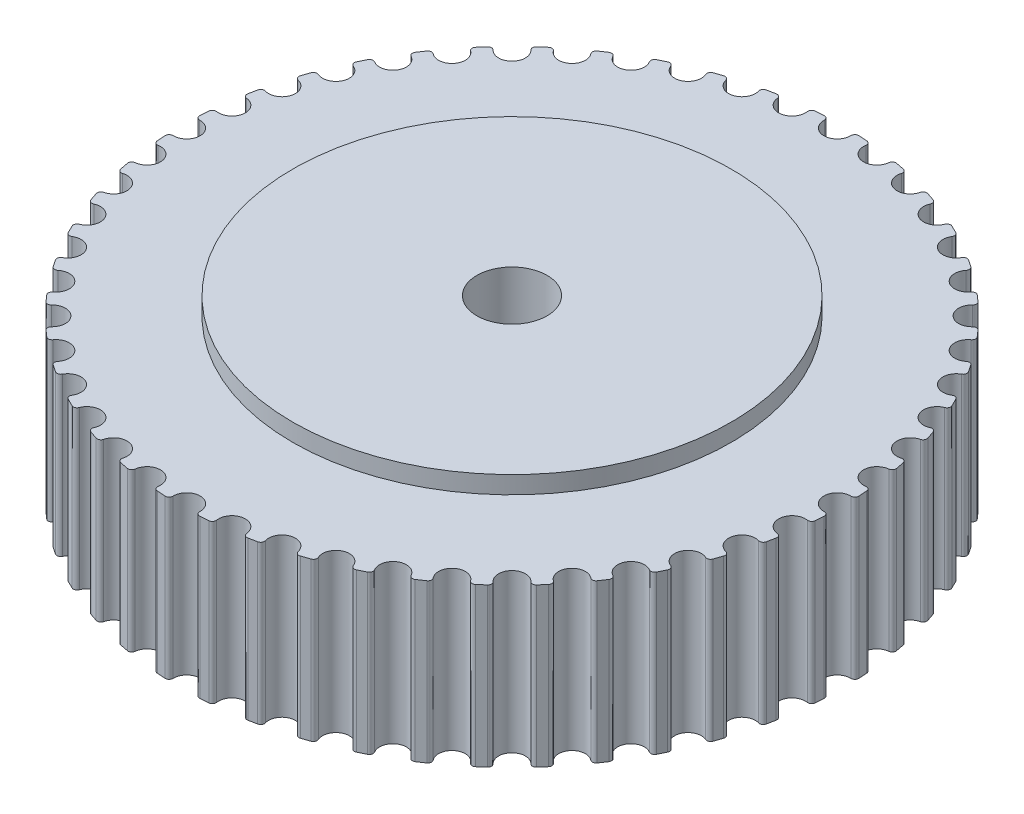
SolidWorks part; units mm, degrees
ref_plane "Ebene vorne" through (0, 0, 0) normal (0, 0, 1) x (1, 0, 0)
ref_plane "Ebene oben" through (0, 0, 0) normal (0, 1, 0) x (1, 0, 0)
ref_plane "Ebene rechts" through (0, 0, 0) normal (1, 0, 0) x (0, 0, -1)
sketch "Skizze1" plane through (0, 0, 0) normal (0, 1, 0) x (1, 0, 0)
  line L0 (0, 0) -> (27482.8107, 0) construction
  line L1 (0, 0) -> (0, 27482.8107) construction
  line L2 (0, 0) -> (8.3206, 63.2012) construction
  line L3 (1.9824, 37.5727) -> (2.9388, 37.51)
  line L4 (6.8697, 36.9925) -> (7.8097, 36.8055)
  line L5 (11.6394, 35.7794) -> (12.547, 35.4713)
  line L6 (16.2099, 33.954) -> (17.0696, 33.5301)
  line L7 (20.5032, 31.5477) -> (21.3001, 31.0152)
  line L8 (24.4455, 28.6016) -> (25.1662, 27.9697)
  line L9 (27.9697, 25.1662) -> (28.6016, 24.4455)
  line L10 (31.0152, 21.3001) -> (31.5477, 20.5032)
  line L11 (33.5301, 17.0696) -> (33.954, 16.2099)
  line L12 (35.4713, 12.547) -> (35.7794, 11.6394)
  line L13 (36.8055, 7.8097) -> (36.9925, 6.8697)
  line L14 (37.51, 2.9388) -> (37.5727, 1.9824)
  line L15 (37.5727, -1.9824) -> (37.51, -2.9388)
  line L16 (36.9925, -6.8697) -> (36.8055, -7.8097)
  line L17 (35.7794, -11.6394) -> (35.4713, -12.547)
  line L18 (33.954, -16.2099) -> (33.5301, -17.0696)
  line L19 (31.5477, -20.5032) -> (31.0152, -21.3001)
  line L20 (28.6016, -24.4455) -> (27.9697, -25.1662)
  line L21 (25.1662, -27.9697) -> (24.4455, -28.6016)
  line L22 (21.3001, -31.0152) -> (20.5032, -31.5477)
  line L23 (17.0696, -33.5301) -> (16.2099, -33.954)
  line L24 (12.547, -35.4713) -> (11.6394, -35.7794)
  line L25 (7.8097, -36.8055) -> (6.8697, -36.9925)
  line L26 (2.9388, -37.51) -> (1.9824, -37.5727)
  line L27 (-1.9824, -37.5727) -> (-2.9388, -37.51)
  line L28 (-6.8697, -36.9925) -> (-7.8097, -36.8055)
  line L29 (-11.6394, -35.7794) -> (-12.547, -35.4713)
  line L30 (-16.2099, -33.954) -> (-17.0696, -33.5301)
  line L31 (-20.5032, -31.5477) -> (-21.3001, -31.0152)
  line L32 (-24.4455, -28.6016) -> (-25.1662, -27.9697)
  line L33 (-27.9697, -25.1662) -> (-28.6016, -24.4455)
  line L34 (-31.0152, -21.3001) -> (-31.5477, -20.5032)
  line L35 (-33.5301, -17.0696) -> (-33.954, -16.2099)
  line L36 (-35.4713, -12.547) -> (-35.7794, -11.6394)
  line L37 (-36.8055, -7.8097) -> (-36.9925, -6.8697)
  line L38 (-37.51, -2.9388) -> (-37.5727, -1.9824)
  line L39 (-37.5727, 1.9824) -> (-37.51, 2.9388)
  line L40 (-36.9925, 6.8697) -> (-36.8055, 7.8097)
  line L41 (-35.7794, 11.6394) -> (-35.4713, 12.547)
  line L42 (-33.954, 16.2099) -> (-33.5301, 17.0696)
  line L43 (-31.5477, 20.5032) -> (-31.0152, 21.3001)
  line L44 (-28.6016, 24.4455) -> (-27.9697, 25.1662)
  line L45 (-25.1662, 27.9697) -> (-24.4455, 28.6016)
  line L46 (-21.3001, 31.0152) -> (-20.5032, 31.5477)
  line L47 (-17.0696, 33.5301) -> (-16.2099, 33.954)
  line L48 (-12.547, 35.4713) -> (-11.6394, 35.7794)
  line L49 (-7.8097, 36.8055) -> (-6.8697, 36.9925)
  line L50 (-2.9388, 37.51) -> (-1.9824, 37.5727)
  circle A0 centre (0, 0) radius 37.625 construction
  circle A1 centre (0, 0) radius 35.565 construction
  arc A2 (0, 35.565) -> (1.5244, 37.1318) centre (0, 37.09) ccw
  arc A3 (1.9824, 37.5727) -> (1.5244, 37.1318) centre (1.9543, 37.1436) ccw
  arc A4 (3.3353, 37.0131) -> (4.6422, 35.2607) centre (4.8412, 36.7727) ccw
  arc A5 (3.3353, 37.0131) -> (2.9388, 37.51) centre (2.9107, 37.0809) ccw
  arc A6 (8.1379, 36.2611) -> (9.2049, 34.3532) centre (9.5996, 35.8262) ccw
  arc A7 (8.1379, 36.2611) -> (7.8097, 36.8055) centre (7.7258, 36.3838) ccw
  arc A8 (6.8697, 36.9925) -> (6.3581, 36.6152) centre (6.7858, 36.5708) ccw
  arc A9 (4.6422, 35.2607) -> (6.3581, 36.6152) centre (4.8412, 36.7727) ccw
  arc A10 (12.8014, 34.8887) -> (13.6101, 32.8578) centre (14.1937, 34.2667) ccw
  arc A11 (12.8014, 34.8887) -> (12.547, 35.4713) centre (12.4087, 35.0641) ccw
  arc A12 (11.6394, 35.7794) -> (11.0829, 35.472) centre (11.5012, 35.3722) ccw
  arc A13 (9.2049, 34.3532) -> (11.0829, 35.472) centre (9.5996, 35.8262) ccw
  arc A14 (17.2457, 32.9193) -> (17.7825, 30.8002) centre (18.545, 32.1209) ccw
  arc A15 (17.2457, 32.9193) -> (17.0696, 33.5301) centre (16.8794, 33.1445) ccw
  arc A16 (16.2099, 33.954) -> (15.6181, 33.722) centre (16.0198, 33.5684) ccw
  arc A17 (13.6101, 32.8578) -> (15.6181, 33.722) centre (14.1937, 34.2667) ccw
  arc A18 (21.395, 30.3867) -> (21.6506, 28.2156) centre (22.579, 29.4255) ccw
  arc A19 (21.395, 30.3867) -> (21.3001, 31.0152) centre (21.0612, 30.6577) ccw
  arc A20 (20.5032, 31.5477) -> (19.8861, 31.3949) centre (20.2643, 31.1902) ccw
  arc A21 (17.7825, 30.8002) -> (19.8861, 31.3949) centre (18.545, 32.1209) ccw
  arc A22 (25.1782, 27.3341) -> (25.1483, 25.1483) centre (26.2266, 26.2266) ccw
  arc A23 (25.1782, 27.3341) -> (25.1662, 27.9697) centre (24.8826, 27.6464) ccw
  arc A24 (24.4455, 28.6016) -> (23.8138, 28.5306) centre (24.162, 28.2783) ccw
  arc A25 (21.6506, 28.2156) -> (23.8138, 28.5306) centre (22.579, 29.4255) ccw
  arc A26 (28.5306, 23.8138) -> (28.2156, 21.6506) centre (29.4255, 22.579) ccw
  arc A27 (28.5306, 23.8138) -> (28.6016, 24.4455) centre (28.2783, 24.162) ccw
  arc A28 (27.9697, 25.1662) -> (27.3341, 25.1782) centre (27.6464, 24.8826) ccw
  arc A29 (25.1483, 25.1483) -> (27.3341, 25.1782) centre (26.2266, 26.2266) ccw
  arc A30 (31.3949, 19.8861) -> (30.8002, 17.7825) centre (32.1209, 18.545) ccw
  arc A31 (31.3949, 19.8861) -> (31.5477, 20.5032) centre (31.1902, 20.2643) ccw
  arc A32 (31.0152, 21.3001) -> (30.3867, 21.395) centre (30.6577, 21.0612) ccw
  arc A33 (28.2156, 21.6506) -> (30.3867, 21.395) centre (29.4255, 22.579) ccw
  arc A34 (33.722, 15.6181) -> (32.8578, 13.6101) centre (34.2667, 14.1937) ccw
  arc A35 (33.722, 15.6181) -> (33.954, 16.2099) centre (33.5684, 16.0198) ccw
  arc A36 (33.5301, 17.0696) -> (32.9193, 17.2457) centre (33.1445, 16.8794) ccw
  arc A37 (30.8002, 17.7825) -> (32.9193, 17.2457) centre (32.1209, 18.545) ccw
  arc A38 (35.472, 11.0829) -> (34.3532, 9.2049) centre (35.8262, 9.5996) ccw
  arc A39 (35.472, 11.0829) -> (35.7794, 11.6394) centre (35.3722, 11.5012) ccw
  arc A40 (35.4713, 12.547) -> (34.8887, 12.8014) centre (35.0641, 12.4087) ccw
  arc A41 (32.8578, 13.6101) -> (34.8887, 12.8014) centre (34.2667, 14.1937) ccw
  arc A42 (36.6152, 6.3581) -> (35.2607, 4.6422) centre (36.7727, 4.8412) ccw
  arc A43 (36.6152, 6.3581) -> (36.9925, 6.8697) centre (36.5708, 6.7858) ccw
  arc A44 (36.8055, 7.8097) -> (36.2611, 8.1379) centre (36.3838, 7.7258) ccw
  arc A45 (34.3532, 9.2049) -> (36.2611, 8.1379) centre (35.8262, 9.5996) ccw
  arc A46 (37.1318, 1.5244) -> (35.565, 0) centre (37.09, 0) ccw
  arc A47 (37.1318, 1.5244) -> (37.5727, 1.9824) centre (37.1436, 1.9543) ccw
  arc A48 (37.51, 2.9388) -> (37.0131, 3.3353) centre (37.0809, 2.9107) ccw
  arc A49 (35.2607, 4.6422) -> (37.0131, 3.3353) centre (36.7727, 4.8412) ccw
  arc A50 (37.0131, -3.3353) -> (35.2607, -4.6422) centre (36.7727, -4.8412) ccw
  arc A51 (37.0131, -3.3353) -> (37.51, -2.9388) centre (37.0809, -2.9107) ccw
  arc A52 (37.5727, -1.9824) -> (37.1318, -1.5244) centre (37.1436, -1.9543) ccw
  arc A53 (35.565, 0) -> (37.1318, -1.5244) centre (37.09, 0) ccw
  arc A54 (36.2611, -8.1379) -> (34.3532, -9.2049) centre (35.8262, -9.5996) ccw
  arc A55 (36.2611, -8.1379) -> (36.8055, -7.8097) centre (36.3838, -7.7258) ccw
  arc A56 (36.9925, -6.8697) -> (36.6152, -6.3581) centre (36.5708, -6.7858) ccw
  arc A57 (35.2607, -4.6422) -> (36.6152, -6.3581) centre (36.7727, -4.8412) ccw
  arc A58 (34.8887, -12.8014) -> (32.8578, -13.6101) centre (34.2667, -14.1937) ccw
  arc A59 (34.8887, -12.8014) -> (35.4713, -12.547) centre (35.0641, -12.4087) ccw
  arc A60 (35.7794, -11.6394) -> (35.472, -11.0829) centre (35.3722, -11.5012) ccw
  arc A61 (34.3532, -9.2049) -> (35.472, -11.0829) centre (35.8262, -9.5996) ccw
  arc A62 (32.9193, -17.2457) -> (30.8002, -17.7825) centre (32.1209, -18.545) ccw
  arc A63 (32.9193, -17.2457) -> (33.5301, -17.0696) centre (33.1445, -16.8794) ccw
  arc A64 (33.954, -16.2099) -> (33.722, -15.6181) centre (33.5684, -16.0198) ccw
  arc A65 (32.8578, -13.6101) -> (33.722, -15.6181) centre (34.2667, -14.1937) ccw
  arc A66 (30.3867, -21.395) -> (28.2156, -21.6506) centre (29.4255, -22.579) ccw
  arc A67 (30.3867, -21.395) -> (31.0152, -21.3001) centre (30.6577, -21.0612) ccw
  arc A68 (31.5477, -20.5032) -> (31.3949, -19.8861) centre (31.1902, -20.2643) ccw
  arc A69 (30.8002, -17.7825) -> (31.3949, -19.8861) centre (32.1209, -18.545) ccw
  arc A70 (27.3341, -25.1782) -> (25.1483, -25.1483) centre (26.2266, -26.2266) ccw
  arc A71 (27.3341, -25.1782) -> (27.9697, -25.1662) centre (27.6464, -24.8826) ccw
  arc A72 (28.6016, -24.4455) -> (28.5306, -23.8138) centre (28.2783, -24.162) ccw
  arc A73 (28.2156, -21.6506) -> (28.5306, -23.8138) centre (29.4255, -22.579) ccw
  arc A74 (23.8138, -28.5306) -> (21.6506, -28.2156) centre (22.579, -29.4255) ccw
  arc A75 (23.8138, -28.5306) -> (24.4455, -28.6016) centre (24.162, -28.2783) ccw
  arc A76 (25.1662, -27.9697) -> (25.1782, -27.3341) centre (24.8826, -27.6464) ccw
  arc A77 (25.1483, -25.1483) -> (25.1782, -27.3341) centre (26.2266, -26.2266) ccw
  arc A78 (19.8861, -31.3949) -> (17.7825, -30.8002) centre (18.545, -32.1209) ccw
  arc A79 (19.8861, -31.3949) -> (20.5032, -31.5477) centre (20.2643, -31.1902) ccw
  arc A80 (21.3001, -31.0152) -> (21.395, -30.3867) centre (21.0612, -30.6577) ccw
  arc A81 (21.6506, -28.2156) -> (21.395, -30.3867) centre (22.579, -29.4255) ccw
  arc A82 (15.6181, -33.722) -> (13.6101, -32.8578) centre (14.1937, -34.2667) ccw
  arc A83 (15.6181, -33.722) -> (16.2099, -33.954) centre (16.0198, -33.5684) ccw
  arc A84 (17.0696, -33.5301) -> (17.2457, -32.9193) centre (16.8794, -33.1445) ccw
  arc A85 (17.7825, -30.8002) -> (17.2457, -32.9193) centre (18.545, -32.1209) ccw
  arc A86 (11.0829, -35.472) -> (9.2049, -34.3532) centre (9.5996, -35.8262) ccw
  arc A87 (11.0829, -35.472) -> (11.6394, -35.7794) centre (11.5012, -35.3722) ccw
  arc A88 (12.547, -35.4713) -> (12.8014, -34.8887) centre (12.4087, -35.0641) ccw
  arc A89 (13.6101, -32.8578) -> (12.8014, -34.8887) centre (14.1937, -34.2667) ccw
  arc A90 (6.3581, -36.6152) -> (4.6422, -35.2607) centre (4.8412, -36.7727) ccw
  arc A91 (6.3581, -36.6152) -> (6.8697, -36.9925) centre (6.7858, -36.5708) ccw
  arc A92 (7.8097, -36.8055) -> (8.1379, -36.2611) centre (7.7258, -36.3838) ccw
  arc A93 (9.2049, -34.3532) -> (8.1379, -36.2611) centre (9.5996, -35.8262) ccw
  arc A94 (1.5244, -37.1318) -> (0, -35.565) centre (0, -37.09) ccw
  arc A95 (1.5244, -37.1318) -> (1.9824, -37.5727) centre (1.9543, -37.1436) ccw
  arc A96 (2.9388, -37.51) -> (3.3353, -37.0131) centre (2.9107, -37.0809) ccw
  arc A97 (4.6422, -35.2607) -> (3.3353, -37.0131) centre (4.8412, -36.7727) ccw
  arc A98 (-3.3353, -37.0131) -> (-4.6422, -35.2607) centre (-4.8412, -36.7727) ccw
  arc A99 (-3.3353, -37.0131) -> (-2.9388, -37.51) centre (-2.9107, -37.0809) ccw
  arc A100 (-1.9824, -37.5727) -> (-1.5244, -37.1318) centre (-1.9543, -37.1436) ccw
  arc A101 (0, -35.565) -> (-1.5244, -37.1318) centre (0, -37.09) ccw
  arc A102 (-8.1379, -36.2611) -> (-9.2049, -34.3532) centre (-9.5996, -35.8262) ccw
  arc A103 (-8.1379, -36.2611) -> (-7.8097, -36.8055) centre (-7.7258, -36.3838) ccw
  arc A104 (-6.8697, -36.9925) -> (-6.3581, -36.6152) centre (-6.7858, -36.5708) ccw
  arc A105 (-4.6422, -35.2607) -> (-6.3581, -36.6152) centre (-4.8412, -36.7727) ccw
  arc A106 (-12.8014, -34.8887) -> (-13.6101, -32.8578) centre (-14.1937, -34.2667) ccw
  arc A107 (-12.8014, -34.8887) -> (-12.547, -35.4713) centre (-12.4087, -35.0641) ccw
  arc A108 (-11.6394, -35.7794) -> (-11.0829, -35.472) centre (-11.5012, -35.3722) ccw
  arc A109 (-9.2049, -34.3532) -> (-11.0829, -35.472) centre (-9.5996, -35.8262) ccw
  arc A110 (-17.2457, -32.9193) -> (-17.7825, -30.8002) centre (-18.545, -32.1209) ccw
  arc A111 (-17.2457, -32.9193) -> (-17.0696, -33.5301) centre (-16.8794, -33.1445) ccw
  arc A112 (-16.2099, -33.954) -> (-15.6181, -33.722) centre (-16.0198, -33.5684) ccw
  arc A113 (-13.6101, -32.8578) -> (-15.6181, -33.722) centre (-14.1937, -34.2667) ccw
  arc A114 (-21.395, -30.3867) -> (-21.6506, -28.2156) centre (-22.579, -29.4255) ccw
  arc A115 (-21.395, -30.3867) -> (-21.3001, -31.0152) centre (-21.0612, -30.6577) ccw
  arc A116 (-20.5032, -31.5477) -> (-19.8861, -31.3949) centre (-20.2643, -31.1902) ccw
  arc A117 (-17.7825, -30.8002) -> (-19.8861, -31.3949) centre (-18.545, -32.1209) ccw
  arc A118 (-25.1782, -27.3341) -> (-25.1483, -25.1483) centre (-26.2266, -26.2266) ccw
  arc A119 (-25.1782, -27.3341) -> (-25.1662, -27.9697) centre (-24.8826, -27.6464) ccw
  arc A120 (-24.4455, -28.6016) -> (-23.8138, -28.5306) centre (-24.162, -28.2783) ccw
  arc A121 (-21.6506, -28.2156) -> (-23.8138, -28.5306) centre (-22.579, -29.4255) ccw
  arc A122 (-28.5306, -23.8138) -> (-28.2156, -21.6506) centre (-29.4255, -22.579) ccw
  arc A123 (-28.5306, -23.8138) -> (-28.6016, -24.4455) centre (-28.2783, -24.162) ccw
  arc A124 (-27.9697, -25.1662) -> (-27.3341, -25.1782) centre (-27.6464, -24.8826) ccw
  arc A125 (-25.1483, -25.1483) -> (-27.3341, -25.1782) centre (-26.2266, -26.2266) ccw
  arc A126 (-31.3949, -19.8861) -> (-30.8002, -17.7825) centre (-32.1209, -18.545) ccw
  arc A127 (-31.3949, -19.8861) -> (-31.5477, -20.5032) centre (-31.1902, -20.2643) ccw
  arc A128 (-31.0152, -21.3001) -> (-30.3867, -21.395) centre (-30.6577, -21.0612) ccw
  arc A129 (-28.2156, -21.6506) -> (-30.3867, -21.395) centre (-29.4255, -22.579) ccw
  arc A130 (-33.722, -15.6181) -> (-32.8578, -13.6101) centre (-34.2667, -14.1937) ccw
  arc A131 (-33.722, -15.6181) -> (-33.954, -16.2099) centre (-33.5684, -16.0198) ccw
  arc A132 (-33.5301, -17.0696) -> (-32.9193, -17.2457) centre (-33.1445, -16.8794) ccw
  arc A133 (-30.8002, -17.7825) -> (-32.9193, -17.2457) centre (-32.1209, -18.545) ccw
  arc A134 (-35.472, -11.0829) -> (-34.3532, -9.2049) centre (-35.8262, -9.5996) ccw
  arc A135 (-35.472, -11.0829) -> (-35.7794, -11.6394) centre (-35.3722, -11.5012) ccw
  arc A136 (-35.4713, -12.547) -> (-34.8887, -12.8014) centre (-35.0641, -12.4087) ccw
  arc A137 (-32.8578, -13.6101) -> (-34.8887, -12.8014) centre (-34.2667, -14.1937) ccw
  arc A138 (-36.6152, -6.3581) -> (-35.2607, -4.6422) centre (-36.7727, -4.8412) ccw
  arc A139 (-36.6152, -6.3581) -> (-36.9925, -6.8697) centre (-36.5708, -6.7858) ccw
  arc A140 (-36.8055, -7.8097) -> (-36.2611, -8.1379) centre (-36.3838, -7.7258) ccw
  arc A141 (-34.3532, -9.2049) -> (-36.2611, -8.1379) centre (-35.8262, -9.5996) ccw
  arc A142 (-37.1318, -1.5244) -> (-35.565, 0) centre (-37.09, 0) ccw
  arc A143 (-37.1318, -1.5244) -> (-37.5727, -1.9824) centre (-37.1436, -1.9543) ccw
  arc A144 (-37.51, -2.9388) -> (-37.0131, -3.3353) centre (-37.0809, -2.9107) ccw
  arc A145 (-35.2607, -4.6422) -> (-37.0131, -3.3353) centre (-36.7727, -4.8412) ccw
  arc A146 (-37.0131, 3.3353) -> (-35.2607, 4.6422) centre (-36.7727, 4.8412) ccw
  arc A147 (-37.0131, 3.3353) -> (-37.51, 2.9388) centre (-37.0809, 2.9107) ccw
  arc A148 (-37.5727, 1.9824) -> (-37.1318, 1.5244) centre (-37.1436, 1.9543) ccw
  arc A149 (-35.565, 0) -> (-37.1318, 1.5244) centre (-37.09, 0) ccw
  arc A150 (-36.2611, 8.1379) -> (-34.3532, 9.2049) centre (-35.8262, 9.5996) ccw
  arc A151 (-36.2611, 8.1379) -> (-36.8055, 7.8097) centre (-36.3838, 7.7258) ccw
  arc A152 (-36.9925, 6.8697) -> (-36.6152, 6.3581) centre (-36.5708, 6.7858) ccw
  arc A153 (-35.2607, 4.6422) -> (-36.6152, 6.3581) centre (-36.7727, 4.8412) ccw
  arc A154 (-34.8887, 12.8014) -> (-32.8578, 13.6101) centre (-34.2667, 14.1937) ccw
  arc A155 (-34.8887, 12.8014) -> (-35.4713, 12.547) centre (-35.0641, 12.4087) ccw
  arc A156 (-35.7794, 11.6394) -> (-35.472, 11.0829) centre (-35.3722, 11.5012) ccw
  arc A157 (-34.3532, 9.2049) -> (-35.472, 11.0829) centre (-35.8262, 9.5996) ccw
  arc A158 (-32.9193, 17.2457) -> (-30.8002, 17.7825) centre (-32.1209, 18.545) ccw
  arc A159 (-32.9193, 17.2457) -> (-33.5301, 17.0696) centre (-33.1445, 16.8794) ccw
  arc A160 (-33.954, 16.2099) -> (-33.722, 15.6181) centre (-33.5684, 16.0198) ccw
  arc A161 (-32.8578, 13.6101) -> (-33.722, 15.6181) centre (-34.2667, 14.1937) ccw
  arc A162 (-30.3867, 21.395) -> (-28.2156, 21.6506) centre (-29.4255, 22.579) ccw
  arc A163 (-30.3867, 21.395) -> (-31.0152, 21.3001) centre (-30.6577, 21.0612) ccw
  arc A164 (-31.5477, 20.5032) -> (-31.3949, 19.8861) centre (-31.1902, 20.2643) ccw
  arc A165 (-30.8002, 17.7825) -> (-31.3949, 19.8861) centre (-32.1209, 18.545) ccw
  arc A166 (-27.3341, 25.1782) -> (-25.1483, 25.1483) centre (-26.2266, 26.2266) ccw
  arc A167 (-27.3341, 25.1782) -> (-27.9697, 25.1662) centre (-27.6464, 24.8826) ccw
  arc A168 (-28.6016, 24.4455) -> (-28.5306, 23.8138) centre (-28.2783, 24.162) ccw
  arc A169 (-28.2156, 21.6506) -> (-28.5306, 23.8138) centre (-29.4255, 22.579) ccw
  arc A170 (-23.8138, 28.5306) -> (-21.6506, 28.2156) centre (-22.579, 29.4255) ccw
  arc A171 (-23.8138, 28.5306) -> (-24.4455, 28.6016) centre (-24.162, 28.2783) ccw
  arc A172 (-25.1662, 27.9697) -> (-25.1782, 27.3341) centre (-24.8826, 27.6464) ccw
  arc A173 (-25.1483, 25.1483) -> (-25.1782, 27.3341) centre (-26.2266, 26.2266) ccw
  arc A174 (-19.8861, 31.3949) -> (-17.7825, 30.8002) centre (-18.545, 32.1209) ccw
  arc A175 (-19.8861, 31.3949) -> (-20.5032, 31.5477) centre (-20.2643, 31.1902) ccw
  arc A176 (-21.3001, 31.0152) -> (-21.395, 30.3867) centre (-21.0612, 30.6577) ccw
  arc A177 (-21.6506, 28.2156) -> (-21.395, 30.3867) centre (-22.579, 29.4255) ccw
  arc A178 (-15.6181, 33.722) -> (-13.6101, 32.8578) centre (-14.1937, 34.2667) ccw
  arc A179 (-15.6181, 33.722) -> (-16.2099, 33.954) centre (-16.0198, 33.5684) ccw
  arc A180 (-17.0696, 33.5301) -> (-17.2457, 32.9193) centre (-16.8794, 33.1445) ccw
  arc A181 (-17.7825, 30.8002) -> (-17.2457, 32.9193) centre (-18.545, 32.1209) ccw
  arc A182 (-11.0829, 35.472) -> (-9.2049, 34.3532) centre (-9.5996, 35.8262) ccw
  arc A183 (-11.0829, 35.472) -> (-11.6394, 35.7794) centre (-11.5012, 35.3722) ccw
  arc A184 (-12.547, 35.4713) -> (-12.8014, 34.8887) centre (-12.4087, 35.0641) ccw
  arc A185 (-13.6101, 32.8578) -> (-12.8014, 34.8887) centre (-14.1937, 34.2667) ccw
  arc A186 (-6.3581, 36.6152) -> (-4.6422, 35.2607) centre (-4.8412, 36.7727) ccw
  arc A187 (-6.3581, 36.6152) -> (-6.8697, 36.9925) centre (-6.7858, 36.5708) ccw
  arc A188 (-7.8097, 36.8055) -> (-8.1379, 36.2611) centre (-7.7258, 36.3838) ccw
  arc A189 (-9.2049, 34.3532) -> (-8.1379, 36.2611) centre (-9.5996, 35.8262) ccw
  arc A190 (-1.5244, 37.1318) -> (0, 35.565) centre (0, 37.09) ccw
  arc A191 (-1.5244, 37.1318) -> (-1.9824, 37.5727) centre (-1.9543, 37.1436) ccw
  arc A192 (-2.9388, 37.51) -> (-3.3353, 37.0131) centre (-2.9107, 37.0809) ccw
  arc A193 (-4.6422, 35.2607) -> (-3.3353, 37.0131) centre (-4.8412, 36.7727) ccw
  point P492 (0, 0)
  dimension "D1" = 75.25
  dimension "D2" = 71.13
  dimension "D3" = 3.05
  dimension "D4" = 0.86
  dimension "D5" = 7.5
  dimension "D6" = 48
extrude "Aufsatz-Linear austragen1" add sketch "Skizze1" along normal blind 18
sketch "Skizze5" plane through (0, 18, 0) normal (0, 1, 0) x (1, 0, 0)
  circle A0 centre (0, 0) radius 25
  dimension "D1" = 50
extrude "Aufsatz-Linear austragen2" add sketch "Skizze5" along normal blind 2
sketch "Skizze6" plane through (0, 0, 0) normal (0, 0, 1) x (1, 0, 0)
  line L0 (0, 0) -> (0, -50000) construction
  line L1 (0, -12) -> (12, -12)
  line L2 (12, -12) -> (12, -2)
  line L5 (12, -2) -> (25, -2)
  line L6 (25, -2) -> (25, 0)
  line L7 (24.4455, 0) -> (25.1662, 0) construction
  line L8 (25, 0) -> (0, 0)
  line L9 (0, 0) -> (0, -12)
  dimension "D1" = 24
  dimension "D3" = 50
  dimension "D4" = 12
  dimension "D5" = 2
revolve "Rotation1" add sketch "Skizze6" angle 360 about L0
hole_wizard "Ø8.0 (8) Durchmesser Bohrung1" positions "Skizze7" profile "Skizze8" hole size "Ø8.0" standard "ISO" end condition through all
sketch "Skizze7" plane through (0, 20, 0) normal (0, 1, 0) x (1, 0, 0)
  point P0 (0, 0)
sketch "Skizze8" plane through (0, 20, 0) normal (1, 0, 0) x (0, 0, 1)
  line L0 (0, 0) -> (0, 32)
  line L1 (0, 32) -> (4, 32)
  line L2 (4, 32) -> (4, 0)
  line L5 (4, 0) -> (0, 0)
  line L11 (0, -6.35) -> (0, 107.95) construction
  dimension "Bohrerdurchmesser" = 8
  dimension "Bohrungstiefe" = 32
hole_wizard "Ø3.1 (3.1) Durchmesser Bohrung1" positions "Skizze9" profile "Skizze10" hole size "Ø3.1" standard "ISO"
sketch "Skizze9" plane through (0, 0, 0) normal (1, 0, 0) x (0, 0, -1)
  line L0 (0, 17.6) -> (0, -17.6) construction
  point P0 (0, -7)
  dimension "D1" = 7
sketch "Skizze10" plane through (0, -7, 0) normal (0, 1, 0) x (0, 0, 1)
  line L0 (0, 0) -> (0, 17.9313)
  line L1 (0, 17.9313) -> (1.55, 17)
  line L2 (1.55, 17) -> (1.55, 0)
  line L5 (1.55, 0) -> (0, 0)
  line L10 (0, 17.9313) -> (-1.55, 17) construction
  line L11 (0, -6.35) -> (0, 107.95) construction
  dimension "Bohrerdurchmesser" = 3.1
  dimension "Bohrungstiefe" = 17
  dimension "Spitzenwinkel" = 118
pattern_circular "Kreismuster1" count 3 over 360 about axis through (0, 0, 0) along (0, 1, 0) of "Ø3.1 (3.1) Durchmesser Bohrung1"
